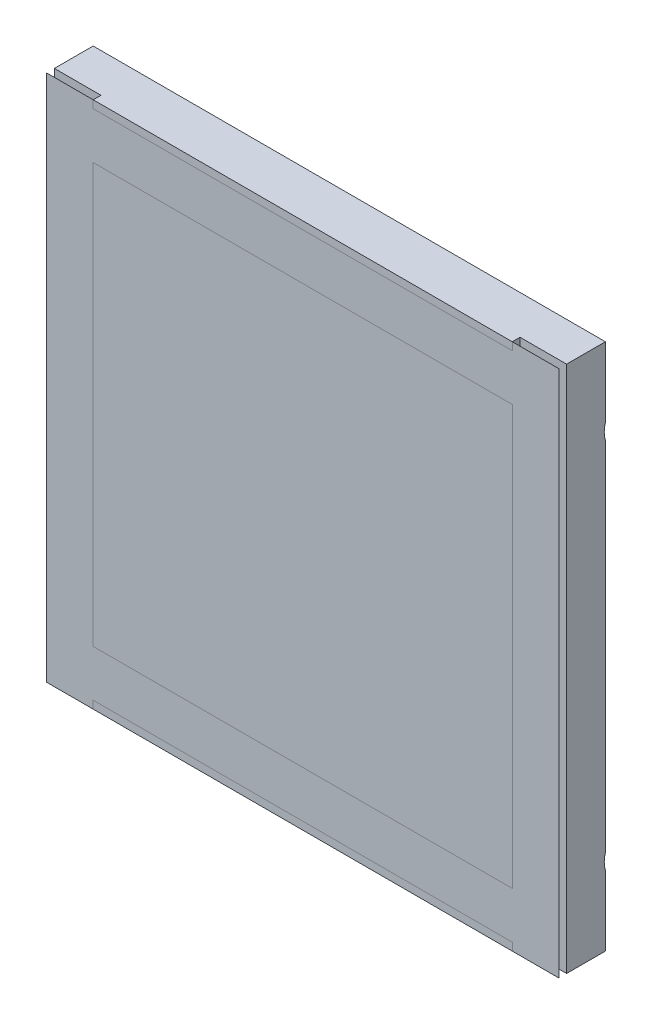
SolidWorks part; units mm, degrees
note: The reader was unsure of these and kept them because the rebuilt part matched: shared geometry of "ｽｹｯﾁ1<3>".
material "3.1325 (EN-AW 2017A)"
ref_plane "正面" through (0, 0, 0) normal (0, 0, 1) x (1, 0, 0)
ref_plane "平面" through (0, 0, 0) normal (0, 1, 0) x (1, 0, 0)
ref_plane "右側面" through (0, 0, 0) normal (1, 0, 0) x (0, 0, -1)
sketch "ｽｹｯﾁ1" plane through (0, 0, 0) normal (0, 0, 1) x (1, 0, 0)
  line L0 (0, 0) -> (0, -59073.83) construction
  line L1 (-34, 34) -> (34, 34) construction
  line L2 (-34, 34) -> (-34, -34) construction
  line L3 (-34, -34) -> (34, -34) construction
  line L4 (34, 34) -> (34, -34) construction
  line L5 (-34, 30) -> (34, 30) construction
  line L6 (-33, 34) -> (33, 34)
  line L7 (-33, -34) -> (33, -34)
  line L8 (-30, 34) -> (-30, -34) construction
  line L9 (0, 0) -> (59073.83, 0) construction
  line L13 (27, 34) -> (27, 33)
  line L14 (33, -34) -> (33, 34)
  line L15 (27, 33) -> (-27, 33)
  line L16 (-27, 27) -> (27, 27)
  line L17 (27, 27) -> (27, -27)
  line L18 (27, -33) -> (-27, -33)
  line L19 (-27, -27) -> (27, -27)
  line L20 (27, -33) -> (27, -34)
  line L21 (-27, -33) -> (-27, -34)
  line L22 (-33, -34) -> (-33, 34)
  line L23 (-27, 34) -> (-27, 33)
  line L24 (-27, 27) -> (-27, -27)
  point P6 (-15, 0)
  point P7 (15, 0)
  point P13 (-24, 30)
  point P14 (0, 34)
  point P15 (-30, -24)
  point P16 (34, 0)
  point P17 (0, 30)
  point P18 (24, 30)
  point P19 (-30, 0)
  point P20 (-30, 24)
  point P29 (24, -30)
  point P35 (0, -30)
  point P42 (-24, -30)
  point P46 (0, 0)
  point P47 (30, -24)
  point P48 (30, 0)
  point P49 (30, 24)
  point P50 (-30, 24)
  point P51 (-30, -24)
  point P52 (30, -24)
  point P53 (30, 24)
  dimension "D1" = 6
  dimension "D2" = 1
  dimension "D3" = 1
  dimension "D4" = 6
  dimension "D5" = 68
  dimension "D6" = 48
  dimension "D7" = 4
  dimension "D8" = 30
  dimension "D9" = 3
  dimension "D10" = 48
extrude "ﾎﾞｽ - 押し出し1" add sketch "ｽｹｯﾁ1" against normal mid plane 6 contours L22 L6 L14 L7
extrude "ｶｯﾄ - 押し出し1" cut sketch "ｽｹｯﾁ1<3>" against normal blind 1 from surface at 3 contours L23 L1 L22 L3 L21 L18 L20 L14 L13 L15 L24 L16 L17 L19 starting at face at (0, 0, 3)
sketch "ｽｹｯﾁ1<3>" plane through (0, 0, 0) normal (0, 0, 1) x (1, 0, 0) same geometry as "ｽｹｯﾁ1"
hole_wizard "M3 丸皿ねじ用皿穴1" positions "3Dｽｹｯﾁ1" profile "ｽｹｯﾁ2" countersink size "M3" standard "JIS" end condition through all
sketch3d "3Dｽｹｯﾁ1"
  point P39 (24, 30, -3)
  point P41 (0, 30, -3)
  point P43 (-24, 30, -3)
  point P51 (-24, -30, -3)
  point P53 (0, -30, -3)
  point P55 (24, -30, -3)
  point P57 (-24, -30, -3)
  point P59 (0, -30, -3)
  point P61 (24, -30, -3)
  point P79 (30, 24, -3)
  point P81 (30, -24, -3)
  point P83 (-30, -24, -3)
  point P85 (-30, 24, -3)
sketch "ｽｹｯﾁ2" plane through (24, 30, -3) normal (1, 0, 0) x (0, 1, 0)
  line L0 (0, 0) -> (0, 6)
  line L1 (0, 6) -> (1.6, 6)
  line L2 (1.6, 6) -> (1.6, 1.55)
  line L3 (1.6, 1.55) -> (3.15, 0)
  line L5 (3.15, 0) -> (0, 0)
  line L6 (-1.6, 1.55) -> (-3.15, 0) construction
  line L11 (0, -6.35) -> (0, 107.95) construction
  dimension "通し穴の直径" = 3.2
  dimension "通し穴の深さ" = 6
  dimension "表面の皿穴の直径" = 6.3
  dimension "表面の皿穴の角度" = 90
hole_wizard "M3x0.5 ねじ穴1" positions "3Dｽｹｯﾁ2" profile "ｽｹｯﾁ3" tap size "M3x0.5" standard "JIS"
sketch3d "3Dｽｹｯﾁ2"
  point P8 (-15, -34, 0)
  point P10 (15, -34, 0)
sketch "ｽｹｯﾁ3" plane through (-15, -34, 0) normal (1, 0, 0) x (0, 0, -1)
  line L0 (0, 0) -> (0, 9.2511)
  line L1 (0, 9.2511) -> (1.25, 8.5)
  line L2 (1.25, 8.5) -> (1.25, 6)
  line L3 (1.25, 6) -> (1.5, 6)
  line L4 (1.5, 6) -> (1.5, 0)
  line L5 (1.5, 0) -> (0, 0)
  line L10 (0, 9.2511) -> (-1.25, 8.5) construction
  line L11 (0, -6.35) -> (0, 107.95) construction
  dimension "ねじ下穴ﾄﾞﾘﾙ直径" = 2.5
  dimension "ねじ下穴ﾄﾞﾘﾙの深さ" = 8.5
  dimension "ねじ山の主要直径" = 3
  dimension "ねじ山の深さ" = 6
  dimension "ﾄﾞﾘﾙ角度" = 118
sketch "ｽｹｯﾁ4" plane through (0, 0, 3) normal (0, 0, 1) x (1, 0, 0)
  line L0 (13.9802, 0) -> (0, 0) construction
  line L1 (0, 0) -> (0, 15.8476) construction
  line L8 (-28.05, -35.05) -> (-34.05, -35.05)
  line L9 (-34.05, -35.05) -> (-34.05, 35.05)
  line L10 (-34.05, 35.05) -> (-28.05, 35.05)
  line L11 (27, -35.05) -> (34.05, -35.05)
  line L12 (27, 34) -> (27, 33)
  line L13 (27, 33) -> (-27, 33)
  line L14 (-27, 33) -> (-27, 34)
  line L15 (-27, 34) -> (-33, 34)
  line L16 (-33, 34) -> (-33, -34)
  line L17 (-33, -34) -> (-27, -34)
  line L18 (-27, -34) -> (-27, -33)
  line L19 (-27, -33) -> (27, -33)
  line L20 (27, -33) -> (27, -34)
  line L21 (27, -34) -> (33, -34)
  line L22 (33, -34) -> (33, 34)
  line L23 (33, 34) -> (27, 34)
  line L24 (27, 34) -> (27, 33)
  line L25 (27, 33) -> (-27, 33)
  line L26 (-27, 33) -> (-27, 34)
  line L30 (-27, -34) -> (-27, -33)
  line L31 (-27, -33) -> (27, -33)
  line L32 (27, -33) -> (27, -34)
  line L33 (34.05, -35.05) -> (34.05, 35.05)
  line L34 (34.05, 35.05) -> (27, 35.05)
  line L35 (28.05, -35.05) -> (34.05, -35.05)
  line L36 (34.05, -35.05) -> (34.05, 35.05)
  line L37 (34.05, 35.05) -> (28.05, 35.05)
  arc A0 (28.05, 35.05) -> (27, 34) centre (28.05, 34) ccw
  arc A1 (28.05, -35.05) -> (27, -34) centre (28.05, -34) cw
  arc A2 (-28.05, -35.05) -> (-27, -34) centre (-28.05, -34) ccw
  arc A3 (-28.05, 35.05) -> (-27, 34) centre (-28.05, 34) cw
  dimension "D2" = 2.1
  dimension "D1" = 0
  dimension "D3" = 1.05
sketch "ｽｹｯﾁ5" plane through (0, 0, 3) normal (0, 0, 1) x (1, 0, 0)
  line L0 (27, -27) -> (27, 27) construction
  line L1 (27, -27) -> (-27, -27) construction
  line L2 (-27, -27) -> (-27, 27) construction
  line L3 (27, 27) -> (-27, 27) construction
  line L4 (27, -27) -> (27, 27)
  line L5 (27, -27) -> (-27, -27)
  line L6 (-27, -27) -> (-27, 27)
  line L7 (27, 27) -> (-27, 27)
  line L12 (27, 34) -> (27, 33)
  line L13 (27, 33) -> (-27, 33)
  line L14 (-27, 33) -> (-27, 34)
  line L15 (-27, 34) -> (-33, 34)
  line L16 (-33, 34) -> (-33, -34)
  line L17 (-33, -34) -> (-27, -34)
  line L18 (-27, -34) -> (-27, -33)
  line L19 (-27, -33) -> (27, -33)
  line L20 (27, -33) -> (27, -34)
  line L21 (27, -34) -> (33, -34)
  line L22 (33, -34) -> (33, 34)
  line L23 (33, 34) -> (27, 34)
  line L24 (27, 34) -> (27, 33)
  line L25 (27, 33) -> (-27, 33)
  line L26 (-27, 33) -> (-27, 34)
  line L27 (-27, 34) -> (-33, 34)
  line L28 (-33, 34) -> (-33, -34)
  line L29 (-33, -34) -> (-27, -34)
  line L30 (-27, -34) -> (-27, -33)
  line L31 (-27, -33) -> (27, -33)
  line L32 (27, -33) -> (27, -34)
  line L33 (27, -34) -> (33, -34)
  line L34 (33, -34) -> (33, 34)
  line L35 (33, 34) -> (27, 34)
  dimension "D1" = 0
surface "ｻｰﾌｪｽ-平面1" sketch "ｽｹｯﾁ5"
